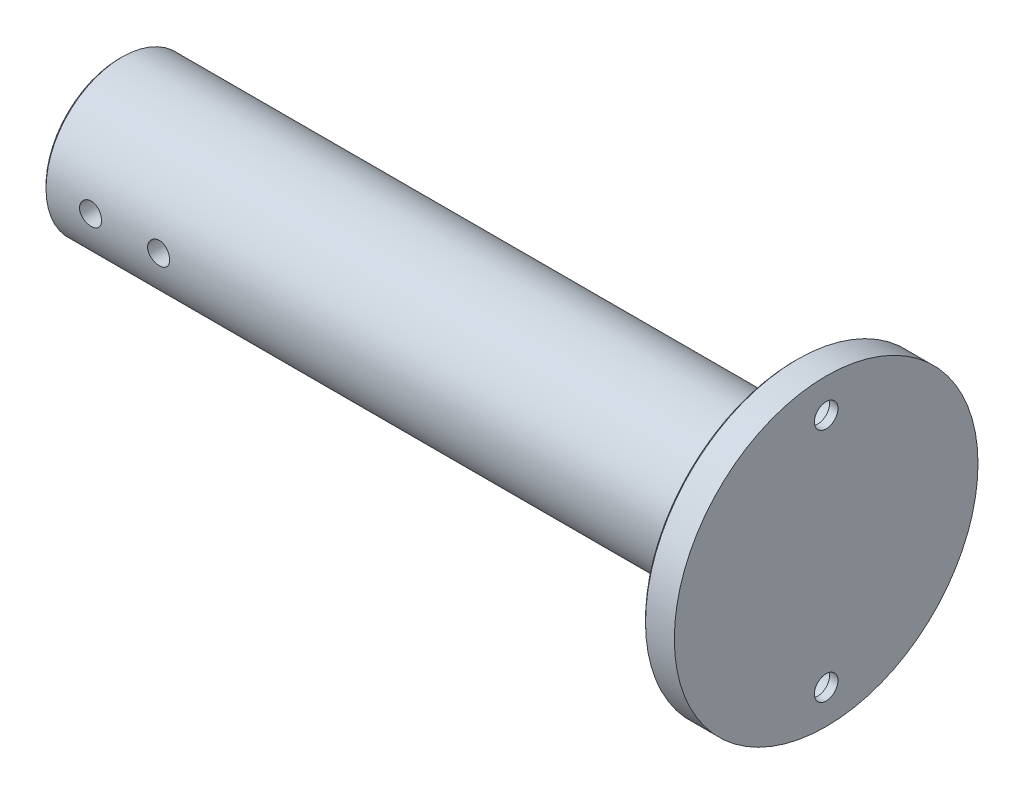
SolidWorks part; units mm, degrees
ref_plane "Plan de face" through (0, 0, 0) normal (0, 0, 1) x (1, 0, 0)
ref_plane "Plan de dessus" through (0, 0, 0) normal (0, 1, 0) x (1, 0, 0)
ref_plane "Plan de droite" through (0, 0, 0) normal (1, 0, 0) x (0, 0, -1)
sketch "Esquisse1" plane through (0, 0, 0) normal (0, 0, 1) x (1, 0, 0)
  line L0 (0, 14.5) -> (129, 14.5)
  line L1 (129, 14.5) -> (129, 29)
  line L2 (129, 29) -> (135, 29)
  line L3 (135, 29) -> (135, 7)
  line L4 (135, 7) -> (0, 7)
  line L5 (0, 7) -> (0, 14.5)
  line L6 (0, 0) -> (41.6495, 0) construction
  dimension "D1" = 135
  dimension "D2" = 14
  dimension "D3" = 7.5
  dimension "D4" = 22
  dimension "D5" = 6
revolve "Révolution1" add sketch "Esquisse1" angle 360 about L6
chamfer "Chanfrein1" distance 0.5 angle 45 2 edges at (129, 0, 29) (0, 0, 14.5)
hole_wizard "Chambrage pour vis à tête hexagonale M41" positions "Esquisse4" profile "Esquisse3" counterbore size "M4" standard "ISO" end condition through all
sketch "Esquisse4" plane through (129, 0, 0) normal (-1, 0, 0) x (0, 0, 1)
  line L0 (0, 22.5) -> (0, 0) construction
  line L1 (0, 0) -> (0, -22.5) construction
  line L2 (0, 4.8641) -> (0, -4.6944) construction
  point P0 (0, -22.5)
  point P2 (0, 22.5)
  dimension "D1" = 45
sketch "Esquisse3" plane through (129, -22.5, 0) normal (0, 1, 0) x (0, 0, 1)
  line L0 (0, 0) -> (0, 6)
  line L1 (0, 6) -> (2.25, 6)
  line L3 (2.25, 6) -> (2.25, 4.4)
  line L4 (2.25, 4.4) -> (4, 4.4)
  line L5 (4, 4.4) -> (4, 0)
  line L7 (4, 0) -> (0, 0)
  line L11 (0, -6.35) -> (0, 107.95) construction
  dimension "Diamètre du perçage jusqu'au prochain" = 4.5
  dimension "Profondeur du perçage jusqu'au prochain" = 6
  dimension "Diamètre du chambrage" = 8
  dimension "Profondeur du chambrage" = 4.4
sketch "Esquisse5" plane through (135, 0, 0) normal (1, 0, 0) x (0, 0, -1)
  circle A0 centre (0, 0) radius 12
  dimension "D1" = 24
extrude "Boss.-Extru.1" add sketch "Esquisse5" against normal offset from surface (105 mm away) 30 up to face at (0, 0, -14)
hole_wizard "Trous de centrage Ø16.0mm1" positions "Esquisse7" profile "Esquisse6" hole size "Ø16.0" standard "ISO"
sketch "Esquisse7" plane through (30, 0, 0) normal (-1, 0, 0) x (0, 0, 1)
  point P0 (0, 0)
sketch "Esquisse6" plane through (30, 0, 0) normal (0, 1, 0) x (0, 0, 1)
  line L0 (0, 0) -> (0, 6.0415)
  line L1 (0, 6.0415) -> (7, 2)
  line L2 (7, 2) -> (7, 0)
  line L5 (7, 0) -> (0, 0)
  line L10 (0, 6.0415) -> (-7, 2) construction
  line L11 (0, -6.35) -> (0, 107.95) construction
  dimension "Diamètre du perçage" = 14
  dimension "Profondeur du perçage" = 2
  dimension "Angle de pointe" = 120
sketch "Esquisse8" plane through (0, 0, 0) normal (0, 0, 1) x (1, 0, 0)
  circle A0 centre (6.75, 0) radius 2.5
  circle A1 centre (22.75, 0) radius 2.5
  dimension "D1" = 5
  dimension "D2" = 6.75
  dimension "D3" = 16
hole_wizard "Trous de centrage Ø4.0mmTransitional 1" [suppressed] positions "Esquisse10" profile "Esquisse9" hole size "Ø4.0" standard "ISO"
sketch "Esquisse10" plane through (129, 0, 0) normal (-1, 0, 0) x (0, 0, 1)
  circle A0 centre (10.4094, 14.0675) radius 2.25 construction
  circle A1 centre (-10.4094, -14.0675) radius 2.25 construction
  point P0 (-16, -8.0675)
  point P2 (16, 8.0675)
  dimension "D2" = 6
  dimension "D1" = 6
  dimension "D3" = 16
  dimension "D4" = 16
sketch "Esquisse9" plane through (129, -8.0675, -16) normal (0, 1, 0) x (0, 0, 1)
  line L0 (0, 0) -> (0, 6)
  line L1 (0, 6) -> (2, 6)
  line L2 (2, 6) -> (2, 0)
  line L5 (2, 0) -> (0, 0)
  line L11 (0, -6.35) -> (0, 107.95) construction
  dimension "Diamètre du perçage jusqu'au prochain" = 4
  dimension "Profondeur du perçage jusqu'au prochain" = 6
sketch "Esquisse12" plane through (0, 0, 0) normal (-1, 0, 0) x (0, 0, 1)
  line L0 (6.5383, 2.5) -> (9.3, 2.5)
  line L1 (6.5383, -2.5) -> (9.3, -2.5)
  line L2 (9.3, 2.5) -> (9.3, -2.5)
  line L3 (-32.4659, 0) -> (38.9443, 0) construction
  circle A0 centre (0, 0) radius 7 construction
  arc A1 (6.5383, 2.5) -> (6.5383, -2.5) centre (0, 0) cw
  circle A2 centre (0, 0) radius 7 construction
  dimension "D1" = 5
  dimension "D2" = 9.3
extrude "Enlèv. mat.-Extru.1" cut sketch "Esquisse12" against normal blind 30
hole_wizard "Trou taraudé M51" positions "Esquisse3D1" profile "Esquisse11" tap size "M5" standard "ISO"
sketch3d "Esquisse3D1"
  line L0 (44.4581, 0, 9.3) -> (-33.3043, 0, 9.3) construction
  line L4 (30, 2.5, 9.3) -> (0, 2.5, 9.3) construction
  line L5 (30, -2.5, 9.3) -> (0, -2.5, 9.3) construction
  line L6 (0, -2.5, 9.3) -> (0, 2.5, 9.3) construction
  point P0 (9, 0, 9.3)
  point P2 (22, 0, 9.3)
  dimension "D1" = 13
  dimension "D2" = 9
sketch "Esquisse11" plane through (9, 0, 9.3) normal (1, 0, 0) x (0, 1, 0)
  line L0 (0, 0) -> (0, 15.2618)
  line L1 (0, 15.2618) -> (2.1, 14)
  line L2 (2.1, 14) -> (2.1, 0)
  line L5 (2.1, 0) -> (0, 0)
  line L10 (0, 15.2618) -> (-2.1, 14) construction
  line L11 (0, -6.35) -> (0, 107.95) construction
  dimension "Diamètre du trou pour taraudage" = 4.2
  dimension "Profondeur du trou pour taraudage" = 14
  dimension "Angle de pointe" = 118
cosmetic thread "Filetage de perçage3" parameters "D1"=5.3224, "D2"=5
cosmetic thread "Filetage de perçage4" parameters "D1"=5.3224, "D2"=5
